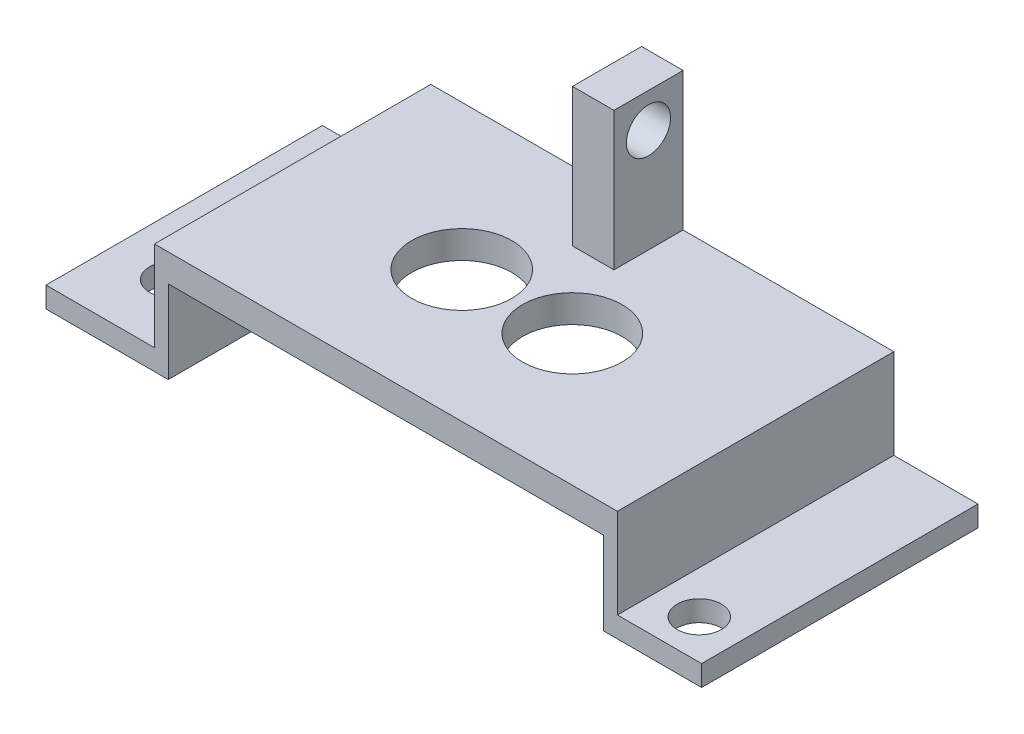
SolidWorks part; units mm, degrees
ref_plane "前视基准面" through (0, 0, 0) normal (0, 0, 1) x (1, 0, 0)
ref_plane "上视基准面" through (0, 0, 0) normal (0, 1, 0) x (1, 0, 0)
ref_plane "右视基准面" through (0, 0, 0) normal (1, 0, 0) x (0, 0, -1)
sketch "草图1" plane through (0, 0, 0) normal (0, 1, 0) x (1, 0, 0)
  line L1 (15.75, -7.5) -> (-15.75, -7.5)
  line L2 (15.75, -7.5) -> (15.75, 7.5)
  line L3 (15.75, 7.5) -> (-15.75, 7.5)
  line L4 (-15.75, -7.5) -> (-15.75, 7.5)
  line L5 (15.75, -7.5) -> (-15.75, 7.5) construction
  line L6 (15.75, 7.5) -> (-15.75, -7.5) construction
  line L7 (-15.75, 7.5) -> (-16.75, 7.5)
  line L8 (-15.75, 7.5) -> (-15.75, -7.5)
  line L9 (-15.75, -7.5) -> (-16.75, -7.5)
  line L10 (-16.75, 7.5) -> (-16.75, -7.5)
  line L11 (15.75, 7.5) -> (16.75, 7.5)
  line L12 (15.75, 7.5) -> (15.75, -7.5)
  line L13 (15.75, -7.5) -> (16.75, -7.5)
  line L14 (16.75, 7.5) -> (16.75, -7.5)
  circle A0 centre (-4.0325, 2.0183) radius 3.625
  circle A1 centre (3.9681, 2.0183) radius 3.6023
  point P0 (0, 0)
  dimension "D1" = 15
  dimension "D2" = 31.5
  dimension "D3" = 1
  dimension "D4" = 1
extrude "凸台-拉伸1" add sketch "草图1" along normal blind 2 contours L4 L1 L2 L3 | L14 L11 L2 L13 | L7 L10 L9 L4 region at (0.012, 0, 0.4241) region at (16.25, 0, 0) region at (-16.25, 0, 0)
extrude "凸台-拉伸2" add sketch "草图1<3>" against normal blind 6 contours L7 L10 L9 L4 | L14 L11 L2 L13 region at (16.25, 0, 0) region at (-16.25, 0, 0)
sketch "草图1<3>" plane through (0, 0, 0) normal (0, 1, 0) x (1, 0, 0) same geometry as "草图1"
sketch "草图2" plane through (0, -6, 0) normal (0, -1, 0) x (1, 0, 0)
  line L0 (-16.75, -7.5) -> (-24.5972, -7.5)
  line L1 (16.75, 7.5) -> (22.8427, 7.5)
  line L2 (16.75, 7.5) -> (16.75, 0)
  line L4 (22.8427, 7.5) -> (22.8427, 0)
  line L5 (-16.75, 7.5) -> (-24.5972, 7.5)
  line L6 (-16.75, 7.5) -> (-16.75, 0)
  line L8 (-24.5972, 7.5) -> (-24.5972, 0)
  line L9 (-24.5972, -7.5) -> (-24.5972, 0)
  line L10 (16.75, -7.5) -> (22.8427, -7.5)
  line L11 (22.8427, -7.5) -> (22.8427, 0)
  line L12 (-16.75, 0) -> (-16.75, -7.5)
  line L13 (16.75, 0) -> (16.75, -7.5)
  circle A0 centre (-20.3951, 2.6105) radius 1.6
  circle A1 centre (19.8267, 4.6519) radius 1.6
extrude "凸台-拉伸3" add sketch "草图2" against normal blind 1.5
sketch "草图3" plane through (0, 0, -7.5) normal (0, 0, -1) x (-1, 0, 0)
  line L8 (-16.75, 2) -> (-16.75, -4.5)
  line L9 (-22.8427, -6) -> (-15.75, -6)
  line L10 (-15.75, -6) -> (-15.75, 0)
  line L11 (-15.75, 0) -> (15.75, 0)
  line L12 (15.75, 0) -> (15.75, -6)
  line L13 (15.75, -6) -> (24.5972, -6)
  line L14 (16.75, -4.5) -> (16.75, 2)
  line L15 (16.75, 2) -> (-16.75, 2)
  line L16 (-16.75, 2) -> (-16.75, -4.5)
  line L17 (-22.8427, -6) -> (-15.75, -6)
  line L18 (-15.75, -6) -> (-15.75, 0)
  line L19 (-15.75, 0) -> (15.75, 0)
  line L20 (15.75, 0) -> (15.75, -6)
  line L21 (15.75, -6) -> (24.5972, -6)
  line L22 (16.75, -4.5) -> (16.75, 2)
  line L23 (16.75, 2) -> (-16.75, 2)
  line L28 (-16.75, -4.5) -> (-22.8427, -4.5)
  line L29 (-16.75, -4.5) -> (-22.8427, -4.5)
  line L30 (-22.8427, -4.5) -> (-22.8427, -6)
  line L31 (-22.8427, -4.5) -> (-22.8427, -6)
  line L32 (24.5972, -6) -> (24.5972, -4.5)
  line L33 (24.5972, -6) -> (24.5972, -4.5)
  line L34 (24.5972, -4.5) -> (16.75, -4.5)
  line L35 (24.5972, -4.5) -> (16.75, -4.5)
  dimension "D1" = 0
extrude "凸台-拉伸4" add sketch "草图3" along normal blind 5
sketch "草图4" plane through (0, 2, 0) normal (0, 1, 0) x (1, 0, 0)
  line L0 (-16.75, 12.5) -> (16.75, 12.5) construction
  line L1 (1.5, 7.5) -> (-1.5, 7.5)
  line L2 (1.5, 7.5) -> (1.5, 12.5)
  line L3 (1.5, 12.5) -> (-1.5, 12.5)
  line L4 (-1.5, 7.5) -> (-1.5, 12.5)
  line L5 (1.5, 7.5) -> (-1.5, 12.5) construction
  line L6 (1.5, 12.5) -> (-1.5, 7.5) construction
  line L7 (0, 5.0269) -> (0, -13.7221) construction
  point P0 (0, 10)
  dimension "D1" = 5
  dimension "D2" = 3
extrude "凸台-拉伸5" add sketch "草图4" along normal blind 10
sketch "草图5" plane through (1.5, 0, 0) normal (1, 0, 0) x (0, 0, -1)
  line L0 (7.5, 12) -> (12.5, 12) construction
  circle A0 centre (10, 9.5) radius 1.6
  dimension "D1" = 3.2
  dimension "D2" = 2.5
extrude "切除-拉伸1" cut sketch "草图5" against normal blind 10
